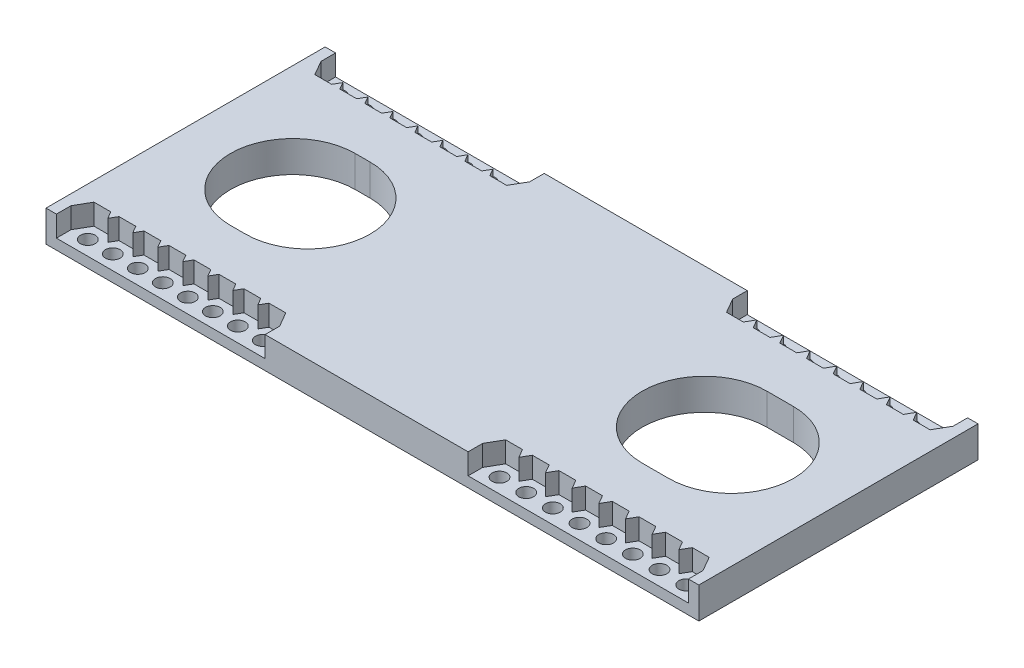
SolidWorks part; units mm, degrees
note: The reader was unsure of these and kept them because the rebuilt part matched: shared geometry of "Sketch1<5>".
ref_plane "Front Plane" through (0, 0, 0) normal (0, 0, 1) x (1, 0, 0)
ref_plane "Top Plane" through (0, 0, 0) normal (0, 1, 0) x (1, 0, 0)
ref_plane "Right Plane" through (0, 0, 0) normal (1, 0, 0) x (0, 0, -1)
sketch "Sketch1" plane through (0, 0, 0) normal (0, 1, 0) x (1, 0, 0)
  line L0 (0, 38.1) -> (0, -38.1) construction
  line L1 (166.116, 38.1) -> (174.244, -38.1) construction
  line L2 (-5.0555, 33.6582) -> (-3.81, 35.8155)
  line L3 (-5.0555, 33.6582) -> (187.9355, 33.6582)
  line L4 (-5.0555, 33.6582) -> (-5.0555, 0)
  line L5 (-5.0555, 0) -> (187.9355, 0)
  line L6 (187.9355, 33.6582) -> (187.9355, 0)
  line L7 (-3.81, 35.8155) -> (-2.5645, 33.6582)
  line L8 (0, 38.1) -> (-3.8467, 35.8791) construction
  line L9 (0, 38.1) -> (3.81, 38.1) construction
  line L10 (3.81, 38.1) -> (7.62, 38.1) construction
  line L11 (7.62, 38.1) -> (7.62, 33.6582) construction
  line L12 (0, 38.1) -> (-3.81, 38.1) construction
  line L13 (2.5645, 33.6582) -> (3.81, 35.8155)
  line L14 (3.81, 35.8155) -> (5.0555, 33.6582)
  line L15 (10.1845, 33.6582) -> (11.43, 35.8155)
  line L16 (11.43, 35.8155) -> (12.6755, 33.6582)
  line L17 (17.8045, 33.6582) -> (19.05, 35.8155)
  line L18 (19.05, 35.8155) -> (20.2955, 33.6582)
  line L19 (25.4245, 33.6582) -> (26.67, 35.8155)
  line L20 (26.67, 35.8155) -> (27.9155, 33.6582)
  line L21 (33.0445, 33.6582) -> (34.29, 35.8155)
  line L22 (34.29, 35.8155) -> (35.5355, 33.6582)
  line L23 (40.6645, 33.6582) -> (41.91, 35.8155)
  line L24 (41.91, 35.8155) -> (43.1555, 33.6582)
  line L25 (48.2845, 33.6582) -> (49.53, 35.8155)
  line L26 (49.53, 35.8155) -> (50.7755, 33.6582)
  line L27 (55.9045, 33.6582) -> (57.15, 35.8155)
  line L28 (57.15, 35.8155) -> (58.3955, 33.6582)
  line L29 (-3.81, 35.8155) -> (3.81, 35.8155) construction
  line L30 (7.62, 38.1) -> (15.24, 38.1) construction
  line L31 (187.9355, 33.6582) -> (186.436, 36.2554)
  line L32 (186.436, 36.2554) -> (184.9365, 33.6582)
  line L33 (182.372, 38.1) -> (186.2187, 35.8791) construction
  line L34 (182.372, 38.1) -> (186.436, 38.1) construction
  line L35 (182.372, 38.1) -> (178.308, 38.1) construction
  line L36 (178.308, 38.1) -> (174.244, 38.1) construction
  line L37 (179.8075, 33.6582) -> (178.308, 36.2554)
  line L38 (178.308, 36.2554) -> (176.8085, 33.6582)
  line L39 (171.6795, 33.6582) -> (170.18, 36.2554)
  line L40 (170.18, 36.2554) -> (168.6805, 33.6582)
  line L41 (163.5515, 33.6582) -> (162.052, 36.2554)
  line L42 (162.052, 36.2554) -> (160.5525, 33.6582)
  line L43 (155.4235, 33.6582) -> (153.924, 36.2554)
  line L44 (153.924, 36.2554) -> (152.4245, 33.6582)
  line L45 (147.2955, 33.6582) -> (145.796, 36.2554)
  line L46 (145.796, 36.2554) -> (144.2965, 33.6582)
  line L47 (139.1675, 33.6582) -> (137.668, 36.2554)
  line L48 (137.668, 36.2554) -> (136.1685, 33.6582)
  line L49 (131.0395, 33.6582) -> (129.54, 36.2554)
  line L50 (129.54, 36.2554) -> (128.0405, 33.6582)
  line L51 (122.9115, 33.6582) -> (121.412, 36.2554)
  line L52 (121.412, 36.2554) -> (119.9125, 33.6582)
  line L53 (-8.304, 42.5418) -> (190.676, 42.5418)
  line L54 (15.24, 42.5418) -> (15.24, 33.6582) construction
  line L55 (-5.129, 42.5418) -> (-5.129, 38.1)
  line L56 (-8.304, 42.5418) -> (-8.304, 0)
  line L58 (186.436, 36.2554) -> (187.501, 38.1)
  line L59 (187.501, 38.1) -> (187.501, 42.5418)
  line L60 (187.9355, 0) -> (190.676, 0)
  line L61 (-5.0555, 0) -> (-8.304, 0)
  line L62 (57.15, 35.8155) -> (58.469, 38.1)
  line L63 (58.469, 38.1) -> (58.469, 42.5418)
  line L64 (121.412, 36.2554) -> (120.347, 38.1)
  line L65 (120.347, 38.1) -> (120.347, 42.5418)
  line L66 (190.676, 42.5418) -> (190.676, 0)
  line L67 (-5.129, 38.1) -> (-3.8467, 35.8791)
  line L68 (-3.8467, 35.8791) -> (-3.81, 35.8155)
  circle A0 centre (0, 38.1) radius 2.2479
  circle A1 centre (0, -38.1) radius 2.2479 construction
  circle A2 centre (7.62, 38.1) radius 2.2479
  circle A3 centre (7.62, -38.1) radius 2.2479 construction
  circle A4 centre (15.24, 38.1) radius 2.2479
  circle A5 centre (15.24, -38.1) radius 2.2479 construction
  circle A6 centre (22.86, 38.1) radius 2.2479
  circle A7 centre (22.86, -38.1) radius 2.2479 construction
  circle A8 centre (30.48, 38.1) radius 2.2479
  circle A9 centre (30.48, -38.1) radius 2.2479 construction
  circle A10 centre (38.1, 38.1) radius 2.2479
  circle A11 centre (38.1, -38.1) radius 2.2479 construction
  circle A12 centre (45.72, 38.1) radius 2.2479
  circle A13 centre (45.72, -38.1) radius 2.2479 construction
  circle A14 centre (53.34, 38.1) radius 2.2479
  circle A15 centre (53.34, -38.1) radius 2.2479 construction
  circle A16 centre (125.476, 38.1) radius 2.2479
  circle A17 centre (125.476, -38.1) radius 2.2479 construction
  circle A18 centre (133.604, 38.1) radius 2.2479
  circle A19 centre (133.604, -38.1) radius 2.2479 construction
  circle A20 centre (141.732, 38.1) radius 2.2479
  circle A21 centre (141.732, -38.1) radius 2.2479 construction
  circle A22 centre (149.86, 38.1) radius 2.2479
  circle A23 centre (149.86, -38.1) radius 2.2479 construction
  circle A24 centre (157.988, 38.1) radius 2.2479
  circle A25 centre (157.988, -38.1) radius 2.2479 construction
  circle A26 centre (166.116, 38.1) radius 2.2479
  circle A27 centre (166.116, -38.1) radius 2.2479 construction
  circle A28 centre (174.244, 38.1) radius 2.2479
  circle A29 centre (174.244, -38.1) radius 2.2479 construction
  circle A30 centre (182.372, 38.1) radius 2.2479
  circle A31 centre (182.372, -38.1) radius 2.2479 construction
  circle A32 centre (15.24, 0) radius 19
  circle A34 centre (15.24, 0) radius 23.544
  point P4 (0, 0)
  point P68 (193.9912, 0)
  point P79 (3.81, 38.1)
  dimension "D1" = 76.2
  dimension "D2" = 4.4958
  dimension "D5" = 8
  dimension "D8" = 38
  dimension "D15" = 3.175
  dimension "D4" = 7.62
  dimension "D6" = 8.128
  dimension "D7" = 127
  dimension "D9" = 4.4418
  dimension "D10" = 120
  dimension "D11" = 9
  dimension "D12" = 120
  dimension "D13" = 9
  dimension "D16" = 3.175
  dimension "D3" = 8
extrude "Boss-Extrude1" add sketch "Sketch1" against normal blind 9.525
extrude "Cut-Extrude1" cut sketch "Sketch1<5>" against normal blind 6.35
sketch "Sketch1<5>" plane through (0, 0, 0) normal (0, 1, 0) x (1, 0, 0) same geometry as "Sketch1"
mirror "Mirror1" about plane through (0, 0, 0) normal (0, 0, 1) of bodies 102
sketch "Sketch2" plane through (0, 0, 0) normal (0, 1, 0) x (1, 0, 0)
  line L0 (157.988, 0) -> (149.86, 0) construction
  line L1 (24.384, 0) -> (28.956, 0) construction
  line L3 (157.988, 0) -> (149.86, 0) construction
  line L4 (157.988, -19) -> (149.86, -19)
  line L5 (157.988, 19) -> (149.86, 19)
  line L6 (28.956, 0) -> (24.384, 0) construction
  line L7 (28.956, -19) -> (24.384, -19)
  line L8 (28.956, 19) -> (24.384, 19)
  arc A2 (157.988, -19) -> (157.988, 19) centre (157.988, 0) ccw
  arc A3 (149.86, 19) -> (149.86, -19) centre (149.86, 0) ccw
  arc A4 (28.956, -19) -> (28.956, 19) centre (28.956, 0) ccw
  arc A5 (24.384, 19) -> (24.384, -19) centre (24.384, 0) ccw
  circle A6 centre (15.24, 0) radius 19 construction
  point P5 (125.476, 38.1)
  point P6 (182.372, 38.1)
  point P8 (53.34, 38.1)
  point P9 (0, 38.1)
  point P12 (153.924, 0)
  point P21 (26.67, 0)
  point P26 (142.1983, 0)
  dimension "D1" = 24.384
  dimension "D2" = 24.384
  dimension "D3" = 24.384
  dimension "D4" = 24.384
extrude "Cut-Extrude2" cut sketch "Sketch2" against normal through all
